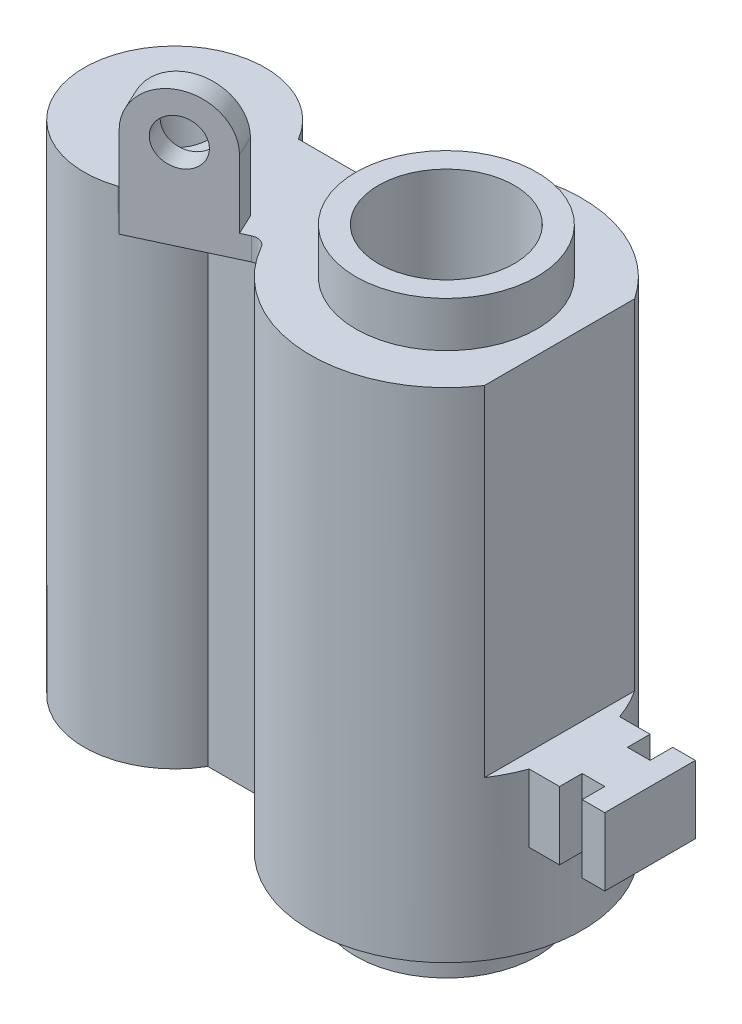
SolidWorks part; units mm, degrees
ref_plane "Front Plane" through (0, 0, 0) normal (0, 0, 1) x (1, 0, 0)
ref_plane "Top Plane" through (0, 0, 0) normal (0, 1, 0) x (1, 0, 0)
ref_plane "Right Plane" through (0, 0, 0) normal (1, 0, 0) x (0, 0, -1)
sketch "Sketch1" plane through (0, 0, 0) normal (0, 1, 0) x (1, 0, 0)
  line L0 (0, 0) -> (-12, 0) construction
  line L1 (-5.6569, 2) -> (-8.5359, 2)
  line L2 (-8.5359, -2) -> (-5.6569, -2)
  circle A0 centre (0, 0) radius 3
  circle A1 centre (0, 0) radius 4
  arc A2 (-5.6569, -2) -> (-5.6569, 2) centre (0, 0) ccw
  arc A3 (-8.5359, 2) -> (-8.5359, -2) centre (-12, 0) ccw
  point P4 (0, 0)
  point P6 (0, 0)
  point P11 (0, 0)
  point P12 (0, 0)
  dimension "D1" = 6
  dimension "D2" = 8
  dimension "D3" = 12
  dimension "D5" = 8
  dimension "D4" = 12
  dimension "D6" = 4
  dimension "D7" = 2
extrude "Boss-Extrude1" add sketch "Sketch1" along normal blind 22 contours L1 A3 L2 A2 A1 region at (-5.4605, 0, 0)
extrude "Boss-Extrude2" add sketch "Sketch1<3>" along normal blind 24 and the other way blind 2 contours A0 A1 region at (-3.8869, 0, 0)
sketch "Sketch1<3>" plane through (0, 0, 0) normal (0, 1, 0) x (1, 0, 0) same geometry as "Sketch1"
ref_plane "Plane1" through (0, 4, 0) normal (0, 1, 0) x (1, 0, 0)
sketch "Sketch2" plane through (0, 4, 0) normal (0, 1, 0) x (1, 0, 0)
  line L0 (5, 3.3166) -> (5, -3.3166)
  line L1 (0, 0) -> (11.161, 0) construction
  line L2 (5.6569, 2) -> (7, 2)
  line L3 (5.6569, -2) -> (7, -2)
  line L4 (8, 2) -> (8, 1)
  line L5 (7, 2) -> (7, 1)
  line L6 (7, -1) -> (8, -1)
  line L7 (7, 1) -> (8, 1)
  line L8 (7, -1) -> (7, -2)
  line L9 (8, -1) -> (8, -2)
  line L10 (8, 2) -> (9, 2)
  line L11 (8, -2) -> (9, -2)
  line L12 (9, 2) -> (9, -2)
  arc A0 (5, -3.3166) -> (5, 3.3166) centre (0, 0) ccw
  arc A1 (-5.6569, -2) -> (-5.6569, 2) centre (0, 0) ccw construction
  point P20 (11.161, 0)
  dimension "D1" = 5
  dimension "D2" = 4
  dimension "D3" = 2
  dimension "D4" = 3
  dimension "D5" = 1
  dimension "D6" = 1
  dimension "D7" = 1
  dimension "D8" = 1
  dimension "D9" = 1
extrude "Cut-Extrude1" cut sketch "Sketch2" along normal blind 18 contours L1 L0 A0 | L0 L1 A0 region at (5.403, 4, -1.2588) region at (5.403, 4, 1.2588)
extrude "Boss-Extrude3" add sketch "Sketch2<3>" along normal blind 3 contours L1 A0 L3 L8 L6 L9 L11 L12 | A0 L1 L12 L10 L4 L7 L5 L2 | L0 A0 region at (7.4307, 4, -0.9261) region at (7.4307, 4, 0.9261)
sketch "Sketch2<3>" plane through (0, 4, 0) normal (0, 1, 0) x (1, 0, 0) same geometry as "Sketch2"
sketch "Sketch3" plane through (0, 0, 1) normal (0, 0, 1) x (1, 0, 0)
  line L0 (8, 7) -> (8, 4) construction
  line L1 (7, 4) -> (8, 4)
  line L2 (7, 4) -> (7, 5)
  line L3 (7, 5) -> (8, 5)
  line L4 (8, 4) -> (8, 5)
  dimension "D1" = 1
extrude "Cut-Extrude2" cut sketch "Sketch3" against normal up to surface (2 mm away) up to face at (7.5, 5.5, -1)
ref_plane "Plane2" through (0, 22, 0) normal (0, 1, 0) x (1, 0, 0)
sketch "Sketch6" plane through (0, 22, 0) normal (0, 1, 0) x (1, 0, 0)
  line L0 (-12, 0) -> (-9.0142, -6.403) construction
  line L1 (-12, 0) -> (0, 0) construction
  line L2 (0, 0) -> (-9.8567, -4.5963)
  line L3 (-10.2793, -3.69) -> (-5.8352, -1.6176)
  line L4 (-5.8352, -1.6176) -> (-5.4125, -2.5239)
  line L5 (-10.2793, -3.69) -> (-10.3095, -3.6252)
  line L6 (-8.5359, -2) -> (-6.6552, -2)
  line L7 (-8.5359, -2) -> (-5.6569, -2) construction
  line L8 (-6.6552, -2) -> (-6.2326, -2.9063)
  line L9 (-10.2793, -3.69) -> (-9.8567, -4.5963)
  arc A0 (-10.3095, -3.6252) -> (-8.5359, -2) centre (-12, 0) ccw
  point P9 (-8, 0)
  point P20 (0, 0)
  dimension "D3" = 4
  dimension "D1" = 65
  dimension "D2" = 1
  dimension "D4" = 3.9988
extrude "Boss-Extrude7" add sketch "Sketch6" against normal blind 1 contours L3 L9 L2 L8 | L3 L8 L2 L4 | A0 L5 L3 L6 region at (-6.0339, 22, 2.262) region at (-8.256, 22, 3.2981) region at (-8.3711, 22, 2.5296)
sketch "Sketch7" plane through (0, 22, 0) normal (0, 1, 0) x (1, 0, 0)
  line L0 (-10.2793, -3.69) -> (-6.6541, -1.9995)
  line L1 (-10.3095, -3.6252) -> (-9.8567, -4.5963) construction
  line L2 (-5.4378, -2.5357) -> (-9.8567, -4.5963) construction
  line L3 (-6.6541, -1.9995) -> (-6.2315, -2.9058)
  line L4 (-10.2793, -3.69) -> (-9.8567, -4.5963)
  line L5 (-9.8567, -4.5963) -> (-6.2315, -2.9058)
  dimension "D1" = 1
  dimension "D2" = 4
extrude "Boss-Extrude8" add sketch "Sketch7" along normal blind 5
sketch "Sketch8" plane through (0, 0, 0) normal (0.4226, 0, 0.9063) x (0.9063, 0, -0.4226)
  line L1 (-6.8909, 22) -> (-14.8757, 22) construction
  line L2 (-10.8757, 21) -> (-10.8757, 27) construction
  line L3 (-6.8757, 27) -> (-6.8757, 22) construction
  circle A0 centre (-8.8757, 25) radius 2
  circle A1 centre (-8.8757, 25) radius 1
  line M5 (-6.8757, 22) -> (-6.8757, 27)
  line M6 (-6.8757, 27) -> (-10.8757, 27)
  line M7 (-10.8757, 27) -> (-10.8757, 21)
  dimension "D4" = 4
  dimension "D5" = 2
  dimension "D1" = 3
  dimension "D2" = 2
  dimension "D3" = 2
extrude "Cut-Extrude8" cut sketch "Sketch8" against normal up to next contours A0 M6 M7 | A0 M5 M6 | A1 region at (-6.6364, 26.5533, 3.0946) region at (-9.4518, 26.5533, 4.4075) region at (-8.0441, 25, 3.751)
fillet "Fillet1" radius 0.5 2 edges at (-5.4378, 21.5, 2.5357) (-10.3095, 21.5, 3.6252)
hole_wizard "Ø4.0mm Dowel Hole1" positions "Sketch9" profile "Sketch10" hole size "Ø4.0" standard "ANSI Metric"
sketch "Sketch9" plane through (0, 0, 0) normal (0, -1, 0) x (-1, 0, 0)
  point P0 (12, 0)
sketch "Sketch10" plane through (-12, 0, 0) normal (1, 0, 0) x (0, 0, -1)
  line L0 (0, 0) -> (0, 7)
  line L1 (0, 7) -> (2, 5.7983)
  line L2 (2, 5.7983) -> (2, 0)
  line L5 (2, 0) -> (0, 0)
  line L10 (0, 7) -> (-2, 5.7983) construction
  line L11 (0, -6.35) -> (0, 107.95) construction
  dimension "Hole Dia." = 4
  dimension "Hole Depth" = 7
  dimension "Drill Angle" = 118
hole_wizard "Ø3.0mm Dowel Hole1" positions "Sketch11" profile "Sketch12" hole size "Ø3.0" standard "ANSI Metric"
sketch "Sketch11" plane through (0, 22, 0) normal (0, 1, 0) x (1, 0, 0)
  point P0 (-12, 0)
sketch "Sketch12" plane through (-12, 22, 0) normal (1, 0, 0) x (0, 0, 1)
  line L0 (0, 0) -> (0, 7)
  line L1 (0, 7) -> (1.5, 6.0987)
  line L2 (1.5, 6.0987) -> (1.5, 0)
  line L5 (1.5, 0) -> (0, 0)
  line L10 (0, 7) -> (-1.5, 6.0987) construction
  line L11 (0, -6.35) -> (0, 107.95) construction
  dimension "Hole Dia." = 3
  dimension "Hole Depth" = 7
  dimension "Drill Angle" = 118
